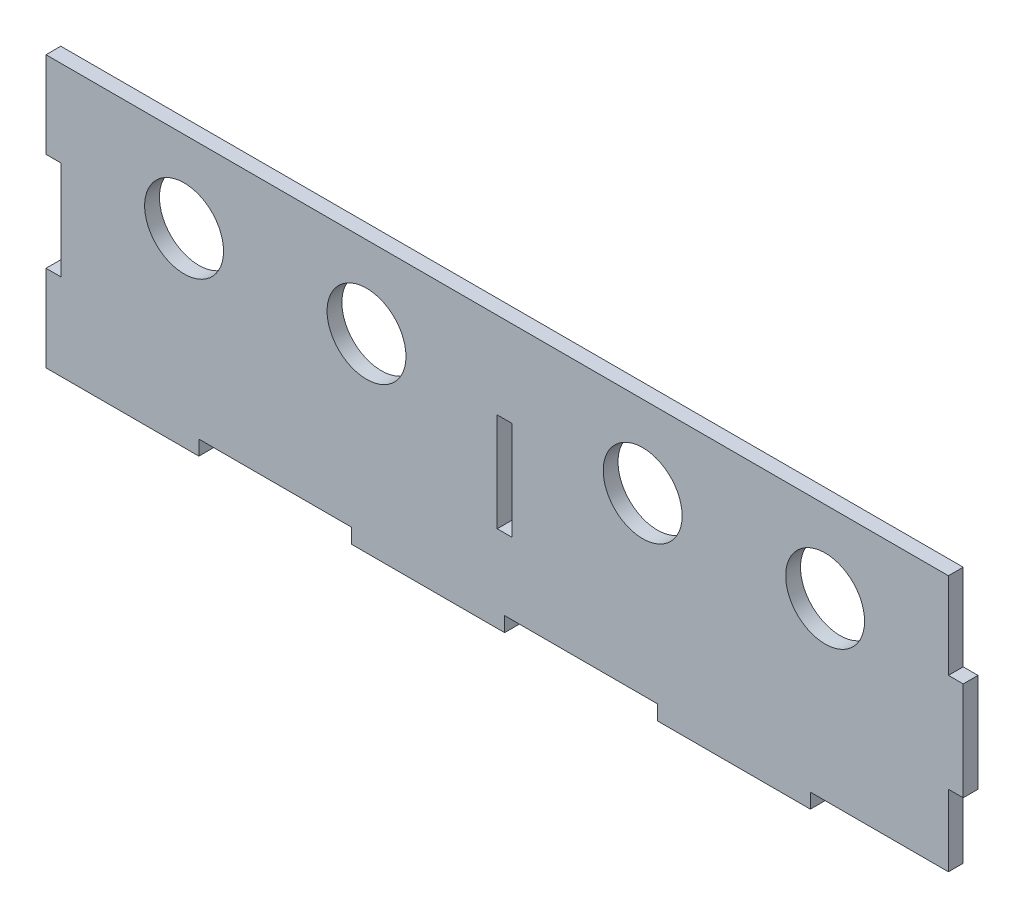
SolidWorks part; units mm, degrees
ref_plane "Front Plane" through (0, 0, 0) normal (0, 0, 1) x (1, 0, 0)
ref_plane "Top Plane" through (0, 0, 0) normal (0, 1, 0) x (1, 0, 0)
ref_plane "Right Plane" through (0, 0, 0) normal (1, 0, 0) x (0, 0, -1)
sketch "Sketch1" plane through (0, 0, 0) normal (0, 0, 1) x (1, 0, 0)
  line L0 (-93, 10) -> (-90, 10)
  line L1 (-93, -27.5) -> (93, -27.5)
  line L2 (-93, -27.5) -> (-93, 27.5)
  line L3 (-93, 27.5) -> (93, 27.5)
  line L4 (93, -27.5) -> (93, 27.5)
  line L5 (-93, -27.5) -> (93, 27.5) construction
  line L6 (-93, 27.5) -> (93, -27.5) construction
  line L7 (-90, 10) -> (-90, -10)
  line L8 (-90, -10) -> (-93, -10)
  line L9 (93, -10) -> (90, -10)
  line L10 (90, -10) -> (90, -27.5)
  line L11 (93, 10) -> (90, 10)
  line L12 (90, 10) -> (90, 27.5)
  line L14 (-62, -27.5) -> (-62, -24.5)
  line L15 (-62, -24.5) -> (-31, -24.5)
  line L16 (-31, -24.5) -> (-31, -27.5)
  line L17 (-93, -27.5) -> (0, -27.5)
  line L18 (0, -27.5) -> (0, -24.5)
  line L19 (0, -24.5) -> (31, -24.5)
  line L20 (31, -24.5) -> (31, -27.5)
  line L21 (-93, -27.5) -> (-93, 27.5)
  line L22 (62, -27.5) -> (62, -24.5)
  line L23 (62, -24.5) -> (93, -24.5)
  line L24 (93, -24.5) -> (93, -27.5)
  line L25 (-93, 27.5) -> (0, 27.5)
  line L26 (-1.5, -10) -> (1.5, -10)
  line L27 (-1.5, -10) -> (-1.5, 10)
  line L28 (-1.5, 10) -> (1.5, 10)
  line L29 (1.5, -10) -> (1.5, 10)
  line L30 (-1.5, -10) -> (1.5, 10) construction
  line L31 (-1.5, 10) -> (1.5, -10) construction
  circle A0 centre (-65, 11) radius 8
  circle A1 centre (-28, 11) radius 8
  circle A2 centre (28, 11) radius 8
  circle A3 centre (65, 11) radius 8
  point P0 (0, 0)
  point P15 (0, 0)
  point P33 (-46.5, 0)
  dimension "D17" = 16.5
  dimension "D18" = 16
  dimension "D20" = 16
  dimension "D27" = 16
  dimension "D28" = 16
  dimension "D1" = 55
  dimension "D2" = 186
  dimension "D3" = 20
  dimension "D4" = 3
  dimension "D5" = 17.5
  dimension "D6" = 3
  dimension "D7" = 3
  dimension "D8" = 31
  dimension "D9" = 31
  dimension "D10" = 31
  dimension "D11" = 31
  dimension "D12" = 31
  dimension "D13" = 31
  dimension "D14" = 3
  dimension "D15" = 20
  dimension "D16" = 3
  dimension "D19" = 28
  dimension "D21" = 16.5
  dimension "D22" = 28
  dimension "D23" = 28
  dimension "D24" = 28
  dimension "D25" = 16.5
  dimension "D26" = 16.5
  dimension "D29" = 37
  dimension "D30" = 37
extrude "Boss-Extrude1" add sketch "Sketch1" along normal blind 3 contours L23 L24 L1 L10 L9 L4 L11 L12 L3 L2 L0 L7 L8 L14 L15 L16 L18 L19 L20 L22 L29 L26 L27 L28 region at (-91.0604, 18.75, 0)
